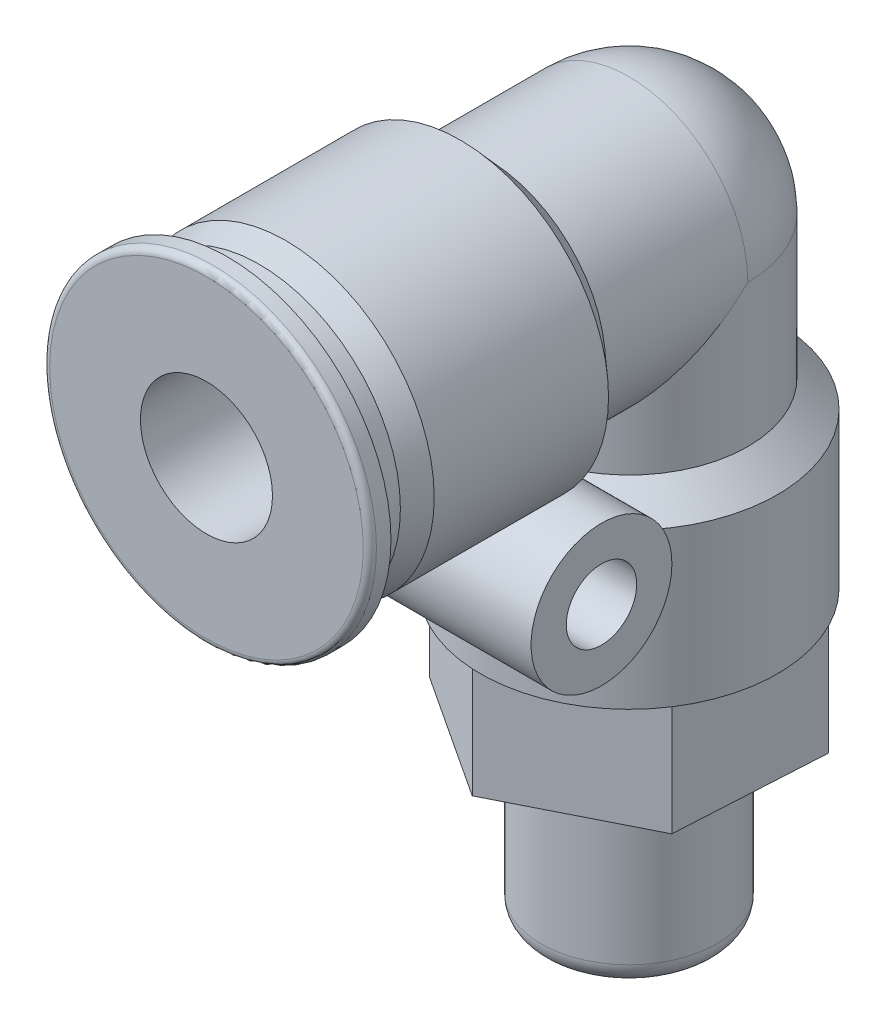
SolidWorks part; units mm, degrees
ref_plane "前视基准面" through (0, 0, 0) normal (0, 0, 1) x (1, 0, 0)
ref_plane "上视基准面" through (0, 0, 0) normal (0, 1, 0) x (1, 0, 0)
ref_plane "右视基准面" through (0, 0, 0) normal (1, 0, 0) x (0, 0, -1)
sketch "草图1" plane through (0, 0, 0) normal (1, 0, 0) x (0, 0, -1)
  line L0 (-19.2, 0) -> (-19.2, 7.125)
  line L1 (-18.9, 7.425) -> (-18.24, 7.425)
  line L2 (-18.24, 7.425) -> (-18.24, 4.5)
  line L3 (-18.24, 4.5) -> (-17.76, 4.5)
  line L4 (-17.76, 4.5) -> (-17.76, 6.2125)
  line L5 (-17.56, 6.4125) -> (-16.8, 6.4125)
  line L6 (-16.8, 6.4125) -> (-15.6, 6.75)
  line L7 (-15.6, 6.75) -> (-7.68, 6.75)
  line L8 (-7.68, 6.75) -> (-6.4645, 5.4)
  line L9 (-6.4645, 5.4) -> (0, 5.4)
  line L10 (5.4, 0) -> (-19.2, 0)
  line L11 (5.4, 0) -> (-19.2, 0) construction
  arc A0 (-19.2, 7.125) -> (-18.9, 7.425) centre (-18.9, 7.125) cw
  arc A1 (-17.76, 6.2125) -> (-17.56, 6.4125) centre (-17.56, 6.2125) cw
  arc A2 (0, 5.4) -> (5.4, 0) centre (0, 0) cw
revolve "旋转1" add sketch "草图1" angle 360 about L11 reverse direction yes
sketch "草图2" plane through (0, 0, 0) normal (1, 0, 0) x (0, 0, -1)
  line L7 (-6.75, -14.7285) -> (-6.75, -7.68)
  line L8 (-6.75, -7.68) -> (-5.4, -6.4645)
  line L9 (-5.4, -6.4645) -> (-5.4, 0)
  line L10 (-5.4, 0) -> (0, 0)
  line L11 (0, 0) -> (0, -14.7285)
  line L12 (0, 0) -> (0, -14.7285) construction
  line L13 (-6.75, -14.7285) -> (0, -14.7285)
revolve "旋转2" add sketch "草图2" angle 360 about L12 reverse direction yes
sketch "草图3" plane through (0, 0, 0) normal (0, 0, 1) x (1, 0, 0)
  circle A0 centre (0, 0) radius 3
extrude "切除-拉伸1" cut sketch "草图3" along normal blind 19.2
sketch "草图5" plane through (0, 0, 0) normal (1, 0, 0) x (0, 0, -1)
  circle A0 centre (-8, -8) radius 3.2
extrude "凸台-拉伸1" add sketch "草图5" against normal blind 6.75 and the other way blind 6.75
sketch "草图6" plane through (0, 0, 0) normal (1, 0, 0) x (0, 0, -1)
  circle A0 centre (-8, -8) radius 1.6
extrude "切除-拉伸2" cut sketch "草图6" along normal blind 6.75 and the other way blind 6.75
sketch "草图4" plane through (0, 0, 0) normal (1, 0, 0) x (0, 0, -1)
  line L0 (3, 0) -> (3, -39.2)
  line L1 (3, -39.2) -> (0, -39.2)
  line L2 (0, -39.2) -> (0, 3)
  line L3 (0, -19.2) -> (0, 3) construction
  arc A0 (0, 3) -> (3, 0) centre (0, 0) cw
revolve "切除-旋转1" cut sketch "草图4" angle 360 about L3 reverse direction yes
sketch "草图7" plane through (0, -14.7285, 0) normal (0, -1, 0) x (1, 0, 0)
  line L1 (-5.6447, -3.7014) -> (0.3832, -6.7391)
  line L2 (0.3832, -6.7391) -> (6.0278, -3.0377)
  line L3 (6.0278, -3.0377) -> (5.6447, 3.7014)
  line L4 (5.6447, 3.7014) -> (-0.3832, 6.7391)
  line L5 (-0.3832, 6.7391) -> (-6.0278, 3.0377)
  line L6 (-6.0278, 3.0377) -> (-5.6447, -3.7014)
  circle A0 centre (0, 0) radius 5.8457 construction
extrude "凸台-拉伸2" add sketch "草图7" along normal blind 5
sketch "草图8" plane through (0, -19.7285, 0) normal (0, -1, 0) x (1, 0, 0)
  circle A0 centre (0, 0) radius 4
  dimension "D1" = 8
extrude "凸台-拉伸3" add sketch "草图8" along normal blind 8
fillet "圆角1" radius 1 1 edges at (0, -27.7285, -4)
